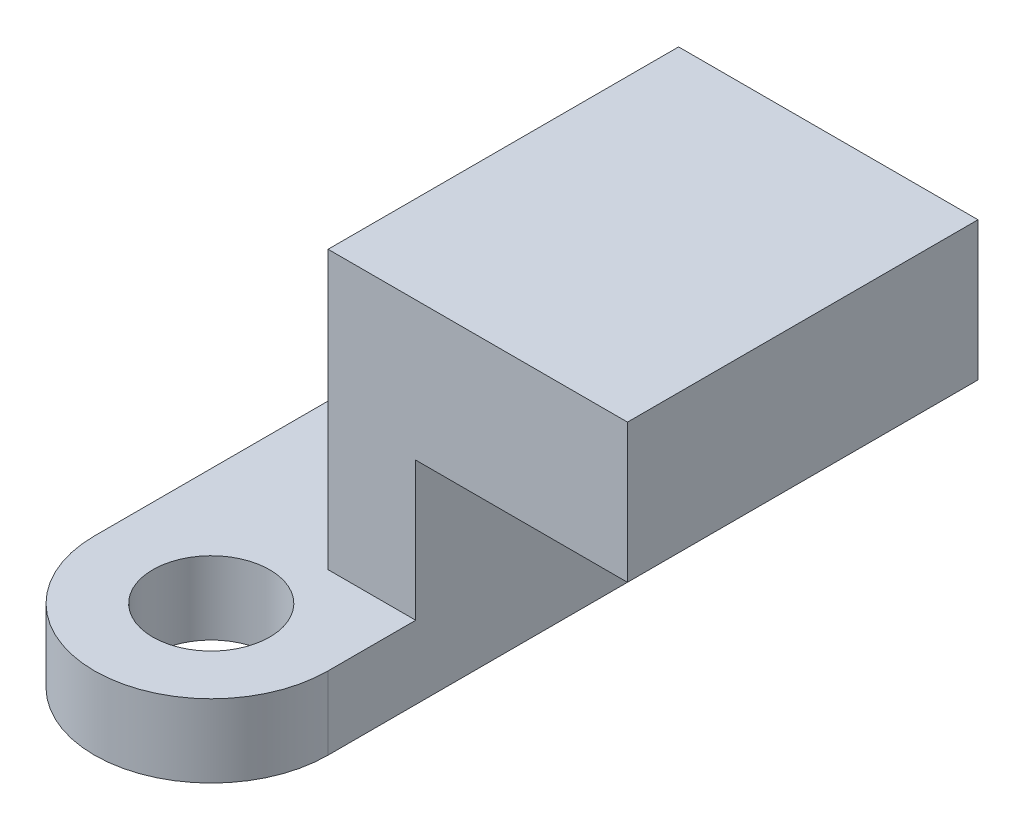
SolidWorks part; units mm, degrees
ref_plane "Front Plane" through (0, 0, 0) normal (0, 0, 1) x (1, 0, 0)
ref_plane "Top Plane" through (0, 0, 0) normal (0, 1, 0) x (1, 0, 0)
ref_plane "Right Plane" through (0, 0, 0) normal (1, 0, 0) x (0, 0, -1)
sketch "Sketch2" plane through (0, 0, 0) normal (0, 1, 0) x (1, 0, 0)
  line L0 (-16, 36) -> (-16, -36)
  line L1 (16, 36) -> (16, -36)
  line L2 (-16, 0) -> (16, 0) construction
  circle A0 centre (0, 36) radius 16
  circle A1 centre (0, -36) radius 16
  circle A2 centre (0, -36) radius 8
  circle A3 centre (0, 36) radius 8
  point P11 (0, 0)
  point P14 (0, 0)
  point P15 (0, 0)
  dimension "D1" = 16
  dimension "D2" = 16
  dimension "D3" = 32
  dimension "D4" = 32
  dimension "D5" = 72
extrude "Boss-Extrude1" add sketch "Sketch2" along normal blind 10 contours A0 A3 | L2 L0 A1 L1 | L0 L2 L1 A0 | A1 A2 region at (0, 0, -11.9889) region at (0, 0, -51.5475) region at (0, 0, 11.9889) region at (0, 0, 20.4525)
sketch "Sketch3" plane through (0, 0, 0) normal (0, 0, 1) x (1, 0, 0)
  line L0 (16, 10) -> (16, 29)
  line L1 (16, 29) -> (45, 29)
  line L2 (45, 29) -> (45, 48)
  line L3 (45, 48) -> (4, 48)
  line L4 (4, 48) -> (4, 10)
  line L6 (16, 10) -> (-16, 10) construction
  line L7 (4, 10) -> (16, 10)
  dimension "D1" = 41
  dimension "D2" = 19
  dimension "D3" = 19
  dimension "D4" = 12
extrude "Boss-Extrude2" add sketch "Sketch3" along normal blind 24 and the other way blind 24
